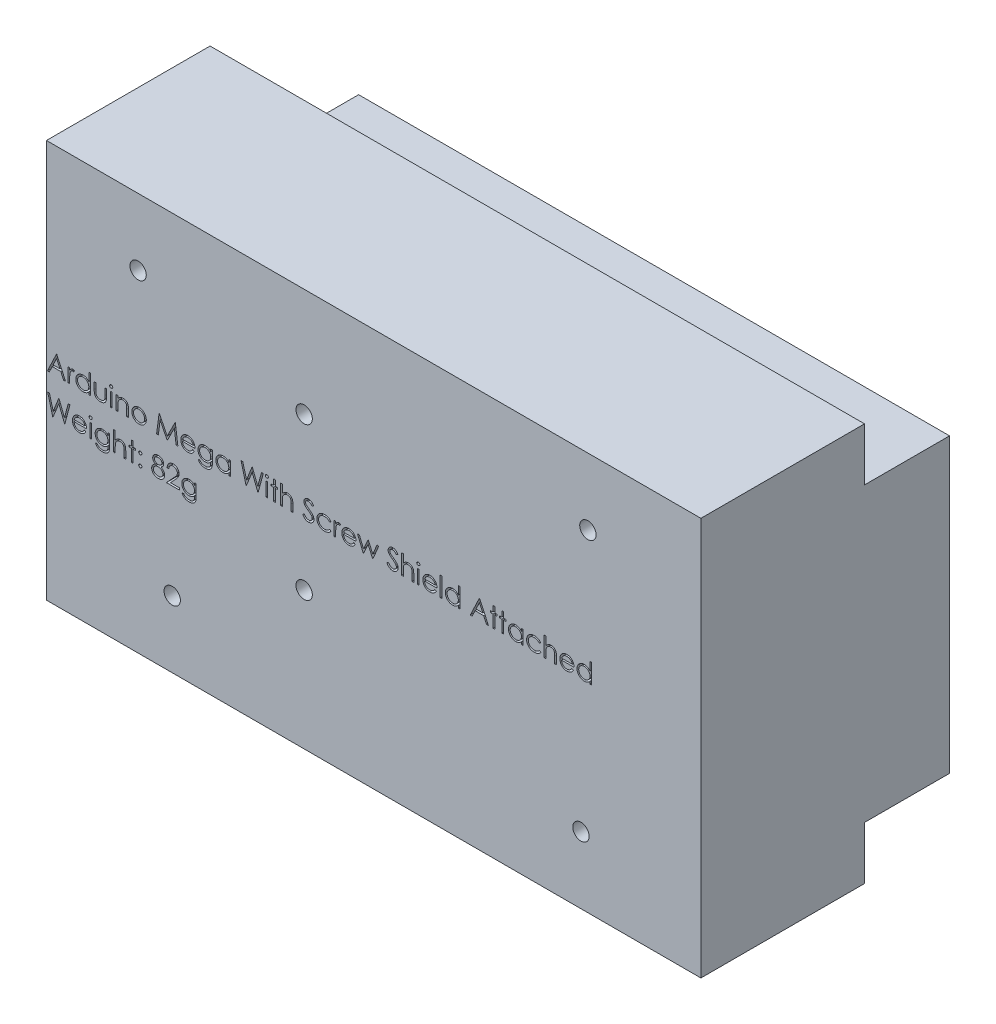
SolidWorks part; units mm, degrees
ref_plane "Front Plane" through (0, 0, 0) normal (0, 0, 1) x (1, 0, 0)
ref_plane "Top Plane" through (0, 0, 0) normal (0, 1, 0) x (1, 0, 0)
ref_plane "Right Plane" through (0, 0, 0) normal (1, 0, 0) x (0, 0, -1)
sketch "Sketch1" plane through (0, 0, 0) normal (0, 0, 1) x (1, 0, 0)
  line L0 (39.28, 24.261) -> (-43.198, 24.261) construction
  line L1 (-60, 36.5) -> (60, 36.5) construction
  line L2 (-60, 36.5) -> (-60, -36.5) construction
  line L3 (-60, -36.5) -> (60, -36.5) construction
  line L4 (60, 36.5) -> (60, -36.5)
  line L5 (0, -36.5) -> (0, 36.5) construction
  line L6 (-60, 0) -> (60, 0) construction
  line L7 (-48.35, -26.8) -> (60, -26.8)
  line L8 (-48.35, -26.8) -> (-48.35, 26.8)
  line L9 (-48.35, 26.8) -> (60, 26.8)
  line L10 (60, -26.8) -> (60, 26.8)
  line L11 (5.825, 26.8) -> (5.825, -26.8) construction
  line L12 (-48.35, 0) -> (60, 0) construction
  line L13 (-12.75, 24.261) -> (-12.75, -26.8) construction
  circle A0 centre (39.28, 24.261) radius 1.5
  circle A1 centre (-43.198, 24.261) radius 1.5
  circle A2 centre (-36.945, -24.261) radius 1.5
  circle A3 centre (38.01, -24.261) radius 1.5
  circle A4 centre (-12.75, 16.644) radius 1.5
  circle A5 centre (-12.75, -11.265) radius 1.5
  point P26 (0, 0)
  point P31 (5.825, 0)
  dimension "D6" = 3
  dimension "D11" = 3
  dimension "D12" = 3
  dimension "D13" = 3
  dimension "D20" = 3
  dimension "D21" = 3
  dimension "D1" = 73
  dimension "D2" = 120
  dimension "D3" = 53.6
  dimension "D4" = 108.35
  dimension "D5" = 0
  dimension "D7" = 2.539
  dimension "D8" = 20.72
  dimension "D9" = 82.478
  dimension "D10" = 48.522
  dimension "D14" = 48.522
  dimension "D15" = 21.99
  dimension "D16" = 11.405
  dimension "D17" = 52.03
  dimension "D18" = 7.617
  dimension "D19" = 27.909
extrude "Boss-Extrude1" add sketch "Sketch1" along normal blind 15.59 contours L9 L8 L7 L4 A5 A4 A3 A2 A1 A0 region at (5.9026, -0.0066, 0)
sketch "Sketch2" plane through (0, 0, 15.59) normal (0, 0, 1) x (1, 0, 0)
  line L0 (39.28, 24.261) -> (-43.198, 24.261) construction
  line L1 (-60, 36.5) -> (60, 36.5)
  line L2 (-60, 36.5) -> (-60, -36.5)
  line L3 (-60, -36.5) -> (60, -36.5)
  line L4 (60, 36.5) -> (60, -36.5)
  line L5 (0, -36.5) -> (0, 36.5) construction
  line L6 (-60, 0) -> (60, 0) construction
  line L7 (-48.35, -26.8) -> (60, -26.8)
  line L8 (-48.35, -26.8) -> (-48.35, 26.8)
  line L9 (-48.35, 26.8) -> (60, 26.8)
  line L10 (60, -26.8) -> (60, 26.8)
  line L11 (5.825, 26.8) -> (5.825, -26.8) construction
  line L12 (-48.35, 0) -> (60, 0) construction
  line L13 (-12.75, 24.261) -> (-12.75, -26.8) construction
  circle A0 centre (39.28, 24.261) radius 1.5
  circle A1 centre (-43.198, 24.261) radius 1.5
  circle A2 centre (-36.945, -24.261) radius 1.5
  circle A3 centre (38.01, -24.261) radius 1.5
  circle A4 centre (-12.75, 16.644) radius 1.5
  circle A5 centre (-12.75, -11.265) radius 1.5
  point P26 (0, 0)
  point P31 (5.825, 0)
  circle M1 centre (-12.75, -11.265) radius 1.5
  circle M2 centre (-12.75, 16.644) radius 1.5
  circle M3 centre (38.01, -24.261) radius 1.5
  circle M4 centre (-36.945, -24.261) radius 1.5
  circle M5 centre (-43.198, 24.261) radius 1.5
  circle M6 centre (39.28, 24.261) radius 1.5
  line M7 (60, 26.8) -> (-48.35, 26.8)
  line M8 (-48.35, 26.8) -> (-48.35, -26.8)
  line M9 (-48.35, -26.8) -> (60, -26.8)
  line M10 (60, -26.8) -> (60, 26.8)
  dimension "D6" = 3
  dimension "D11" = 3
  dimension "D12" = 3
  dimension "D13" = 3
  dimension "D20" = 3
  dimension "D21" = 3
  dimension "D1" = 73
  dimension "D2" = 120
  dimension "D3" = 53.6
  dimension "D4" = 108.35
  dimension "D5" = 0
  dimension "D7" = 2.539
  dimension "D8" = 20.72
  dimension "D9" = 82.478
  dimension "D10" = 48.522
  dimension "D14" = 48.522
  dimension "D15" = 21.99
  dimension "D16" = 11.405
  dimension "D17" = 52.03
  dimension "D18" = 7.617
  dimension "D19" = 27.909
extrude "Boss-Extrude2" add sketch "Sketch2" along normal blind 30 contours L4 L1 L2 L3 M9 M8 M7 | M10 M7 M8 M9 M2 M4 M6 M5 M3 M1 region at (0, 35.0954, 15.59) region at (5.9026, -0.0066, 15.59)
sketch "Sketch3" plane through (0, 0, 45.59) normal (0, 0, 1) x (1, 0, 0)
  line L0 (-60, 0) -> (60, 0) construction
  line L1 (-60, 36.5) -> (-60, -36.5) construction
  line L2 (60, 36.5) -> (60, -36.5) construction
  text T0 "Arduino Mega With Screw Shield Attached\r\nWeight: 82g"
  point P9 (60, -0.8812)
  dimension "D1" = 60
  dimension "D2" = 60
extrude "Cut-Extrude1" cut sketch "Sketch3" against normal blind 2
